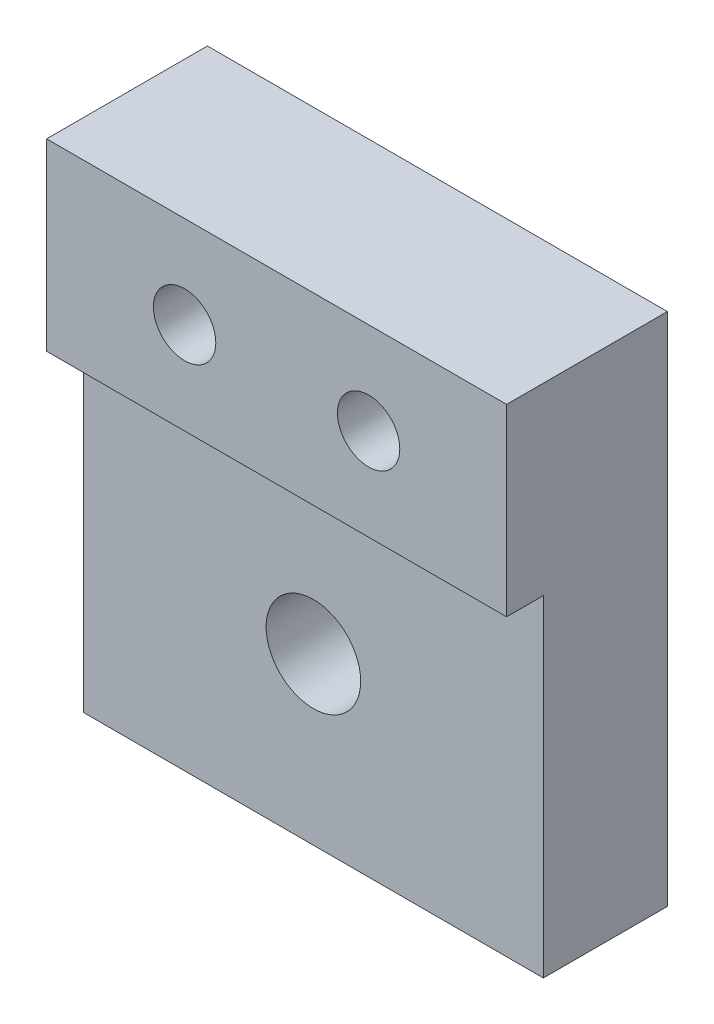
SolidWorks part; units mm, degrees
material "6061-T6 (SS)"
ref_plane "Front Plane" through (0, 0, 0) normal (0, 0, 1) x (1, 0, 0)
ref_plane "Top Plane" through (0, 0, 0) normal (0, 1, 0) x (1, 0, 0)
ref_plane "Right Plane" through (0, 0, 0) normal (1, 0, 0) x (0, 0, -1)
sketch "Sketch1" plane through (0, 0, 0) normal (0, 0, 1) x (1, 0, 0)
  line L2 (0, 22.86) -> (31.75, 22.86)
  line L3 (0, 35.56) -> (31.75, 35.56)
  line L8 (31.75, 0) -> (31.75, 35.56)
  line L10 (0, 35.56) -> (0, 0)
  line L11 (0, 0) -> (31.75, 0)
  circle A3 centre (15.875, 11.43) radius 3.2639
  circle A4 centre (22.225, 29.21) radius 2.1526
  circle A5 centre (9.525, 29.21) radius 2.1527
  dimension "D7" = 4.3053
  dimension "D10" = 6.5278
  dimension "D1" = 35.56
  dimension "D2" = 31.75
  dimension "D3" = 11.43
  dimension "D4" = 15.875
  dimension "D5" = 9.525
  dimension "D6" = 6.35
  dimension "D8" = 9.525
  dimension "D9" = 12.7
extrude "Boss-Extrude1" add sketch "Sketch1" along normal blind 11.0998 contours L3 L10 L2 L8 A5 A4 region at (15.875, 29.21, 0)
extrude "Boss-Extrude2" add sketch "Sketch1<6>" along normal blind 8.5598 contours L10 L11 L8 L2 A3 region at (15.875, 22.4688, 0)
sketch "Sketch1<6>" plane through (0, 0, 0) normal (0, 0, 1) x (1, 0, 0) same geometry as "Sketch1"
